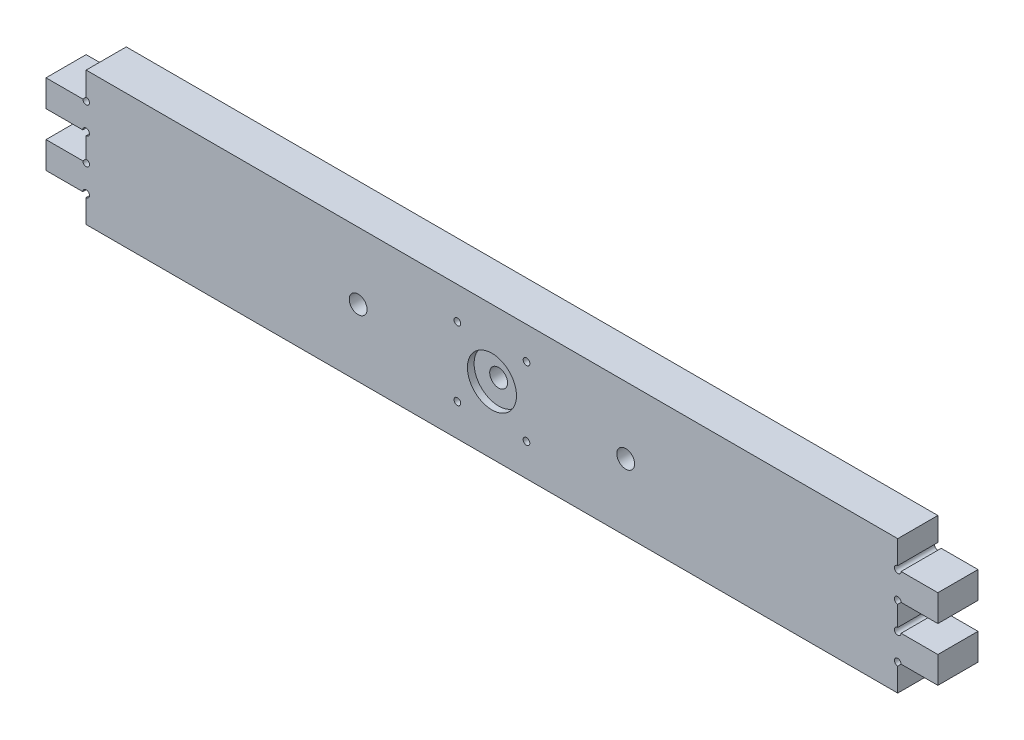
SolidWorks part; units mm, degrees
ref_plane "Front Plane" through (0, 0, 0) normal (0, 0, 1) x (1, 0, 0)
ref_plane "Top Plane" through (0, 0, 0) normal (0, 1, 0) x (1, 0, 0)
ref_plane "Right Plane" through (0, 0, 0) normal (1, 0, 0) x (0, 0, -1)
sketch "Sketch1" plane through (0, 0, 0) normal (0, 0, 1) x (1, 0, 0)
  line L0 (0, -1000) -> (0, 49000) construction
  line L1 (-182, -30) -> (182, -30)
  line L2 (-200, -18) -> (-200, -6)
  line L3 (-182, 30) -> (182, 30)
  line L4 (200, -18) -> (200, -6)
  line L5 (-182, -19.5) -> (-182, -30)
  line L6 (-200, -18) -> (-183.5, -18)
  line L7 (-1000, 0) -> (49000, 0) construction
  line L8 (182, 30) -> (182, 19.5)
  line L9 (200, 18) -> (183.5, 18)
  line L10 (200, 6) -> (183.5, 6)
  line L11 (200, -6) -> (183.5, -6)
  line L12 (200, -18) -> (183.5, -18)
  line L13 (182, 4.5) -> (182, -4.5)
  line L14 (200, 6) -> (200, 18)
  line L15 (200, -30) -> (182, -30) [skipped]
  line L16 (182, -19.5) -> (182, -30)
  line L17 (-200, -6) -> (-183.5, -6)
  line L18 (-182, 4.5) -> (-182, -4.5)
  line L19 (-200, 6) -> (-183.5, 6)
  line L20 (-182, 30) -> (-182, 19.5)
  line L21 (-200, 18) -> (-183.5, 18)
  line L22 (-200, 18) -> (-200, 6)
  line L23 (-200, 6) -> (-200, 18)
  line L24 (-200, -6) -> (-200, -18)
  circle A0 centre (0, 0) radius 4
  circle A1 centre (60, 0) radius 4
  circle A2 centre (-60, 0) radius 4
  arc A3 (182, 19.5) -> (183.5, 18) centre (182, 18) ccw
  arc A4 (183.5, 6) -> (182, 4.5) centre (182, 6) ccw
  arc A5 (182, -4.5) -> (183.5, -6) centre (182, -6) ccw
  arc A6 (183.5, -18) -> (182, -19.5) centre (182, -18) ccw
  arc A7 (-183.5, 18) -> (-182, 19.5) centre (-182, 18) ccw
  arc A8 (-182, 4.5) -> (-183.5, 6) centre (-182, 6) ccw
  arc A9 (-183.5, -6) -> (-182, -4.5) centre (-182, -6) ccw
  arc A10 (-182, -19.5) -> (-183.5, -18) centre (-182, -18) ccw
  point P0 (0, 0)
  point P20 (182, 0)
  dimension "D7" = 8
  dimension "D8" = 8
  dimension "D9" = 8
  dimension "D10" = 60
  dimension "D11" = 60
  dimension "D4" = 3
  dimension "D15" = 3
  dimension "D2" = 60
  dimension "D3" = 18
  dimension "D6" = 400
  dimension "D13" = 18
  dimension "D14" = 16.5
  dimension "D5" = 5
  dimension "D12" = 4
  dimension "D16" = 4
extrude "Boss-Extrude1" add sketch "Sketch1" along normal blind 18 contours L21 L22 L19 L18 L17 L2 L6 L5 L1 L16 L12 L4 L11 L13 L10 L14 L9 L8 L3 L20 A2 A1 A0 region at (-177.9553, -24.75, 0)
sketch "Sketch2" plane through (0, 0, 18) normal (0, 0, 1) x (1, 0, 0)
  line L0 (-1000, 0) -> (49000, 0) construction
  line L1 (0, -1000) -> (0, 49000) construction
  circle A0 centre (15.495, 15.495) radius 1.5
  circle A4 centre (-15.495, 15.495) radius 1.5
  circle A5 centre (15.495, -15.495) radius 1.5
  circle A6 centre (-15.495, -15.495) radius 1.5
  dimension "D1" = 3
  dimension "D2" = 15.495
  dimension "D3" = 15.495
extrude "Cut-Extrude1" cut sketch "Sketch2" against normal up to next
sketch "Sketch3" plane through (0, 0, 18) normal (0, 0, 1) x (1, 0, 0)
  circle A0 centre (0, 0) radius 11
  dimension "D1" = 22
extrude "Cut-Extrude2" cut sketch "Sketch3" against normal blind 3
